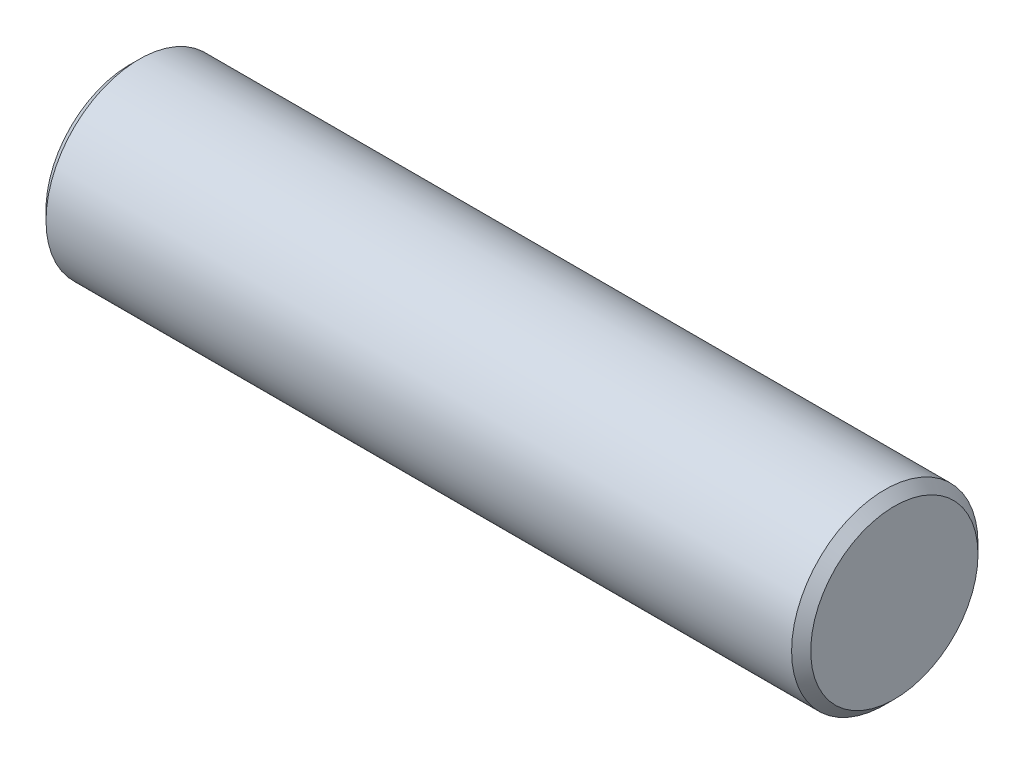
SolidWorks part; units mm, degrees
ref_plane "前视基准面" through (0, 0, 0) normal (0, 0, 1) x (1, 0, 0)
ref_plane "上视基准面" through (0, 0, 0) normal (0, 1, 0) x (1, 0, 0)
ref_plane "右视基准面" through (0, 0, 0) normal (1, 0, 0) x (0, 0, -1)
other "Configuration Table"
sketch "Sketch1" plane through (0, 0, 0) normal (1, 0, 0) x (0, 0, -1)
  circle A0 centre (0, 0) radius 9.75
extrude "Boss-Extrude1" add sketch "Sketch1" along normal blind 80
chamfer "Chamfer1" distance 1 angle 45 2 edges at (80, 0, -9.75) (0, 0, -9.75)
sketch3d "3DSketch1"
  line L0 (0, 0, 0) -> (80, 0, 0) construction
ref_axis "main_axis" through (0, 0, 0) along (1, 0, 0)
ref_plane "end_face" through (0, 0, 0) normal (1, 0, 0) x (0, 0, -1)
